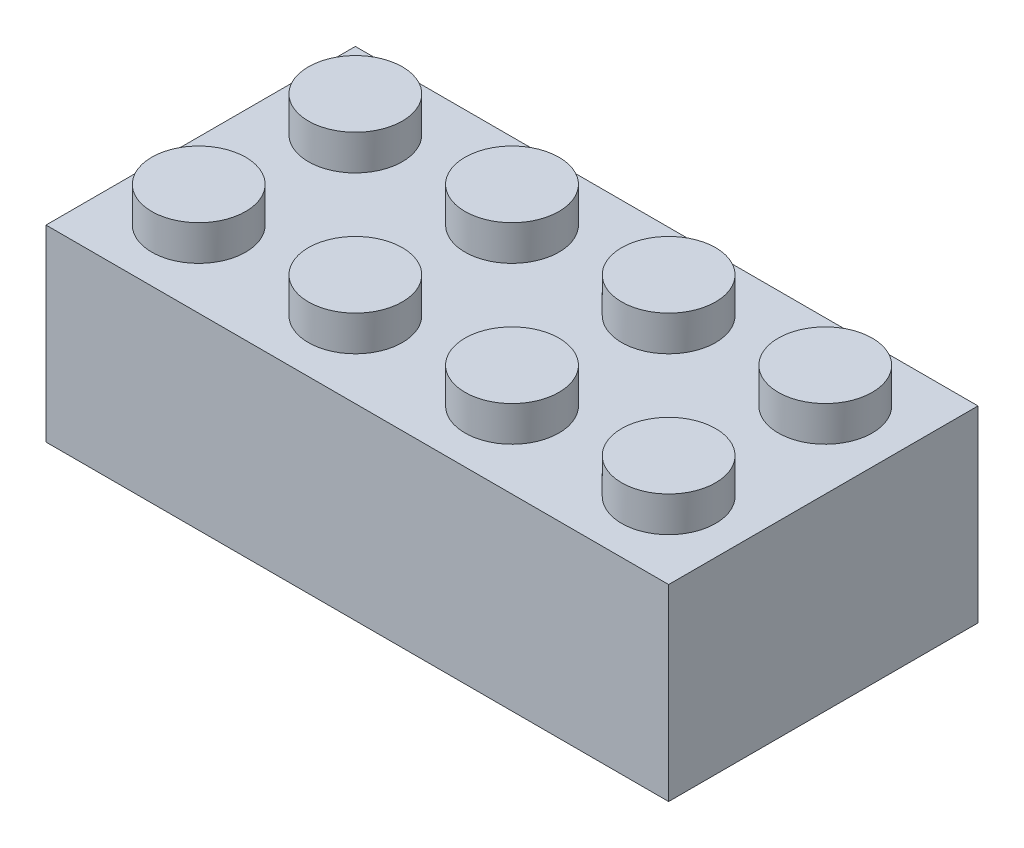
SolidWorks part; units mm, degrees
ref_plane "Front Plane" through (0, 0, 0) normal (0, 0, 1) x (1, 0, 0)
ref_plane "Top Plane" through (0, 0, 0) normal (0, 1, 0) x (1, 0, 0)
ref_plane "Right Plane" through (0, 0, 0) normal (1, 0, 0) x (0, 0, -1)
sketch "Sketch1" plane through (0, 0, 0) normal (0, 1, 0) x (1, 0, 0)
  line L1 (0, 0) -> (31.8, 0)
  line L2 (0, 0) -> (0, 15.8)
  line L3 (0, 15.8) -> (31.8, 15.8)
  line L4 (31.8, 0) -> (31.8, 15.8)
  dimension "D1" = 31.8
  dimension "D2" = 15.8
extrude "Boss-Extrude1" add sketch "Sketch1" along normal blind 9.6
shell "Shell1" thickness 1.2 removed face at (15.9, 0, -7.9)
sketch "Sketch2" plane through (0, 9.6, 0) normal (0, 1, 0) x (1, 0, 0)
  line L0 (31.8, 0) -> (31.8, 15.8) construction
  line L1 (31.8, 15.8) -> (0, 15.8) construction
  circle A0 centre (27.9, 11.9) radius 2.4
  circle A1 centre (19.9, 11.9) radius 2.4
  circle A2 centre (11.9, 11.9) radius 2.4
  circle A3 centre (3.9, 11.9) radius 2.4
  circle A4 centre (19.9, 3.9) radius 2.4
  circle A5 centre (11.9, 3.9) radius 2.4
  circle A6 centre (3.9, 3.9) radius 2.4
  circle A7 centre (27.9, 3.9) radius 2.4
  dimension "D1" = 4.8
  dimension "D2" = 3.9
  dimension "D3" = 3.9
  dimension "D4" = 4
  dimension "D5" = 2
extrude "Boss-Extrude2" add sketch "Sketch2" along normal blind 1.8
sketch "Sketch3" plane through (0, 8.4, 0) normal (0, -1, 0) x (-1, 0, 0)
  line L0 (0, 15.8) -> (0, 0) construction
  line L5 (0, 0) -> (-31.8, 0) construction
  circle A0 centre (-3.9, 3.9) radius 1.4
  circle A1 centre (-11.9, 3.9) radius 1.4
  circle A2 centre (-19.9, 3.9) radius 1.4
  circle A3 centre (-27.9, 3.9) radius 1.4
  circle A4 centre (-11.9, 11.9) radius 1.4
  circle A5 centre (-19.9, 11.9) radius 1.4
  circle A6 centre (-27.9, 11.9) radius 1.4
  circle A7 centre (-3.9, 11.9) radius 1.4
  dimension "D1" = 2.8
  dimension "D2" = 3.9
  dimension "D3" = 3.9
  dimension "D4" = 4
  dimension "D5" = 2
extrude "Cut-Extrude1" cut sketch "Sketch3" against normal blind 1.7
ref_plane "Plane1" through (30.6, 8.4, -1.2) normal (0, 0, -1) x (-1, 0, 0)
sketch "Sketch5" plane through (0, 8.4, 0) normal (0, -1, 0) x (1, 0, 0)
  line L0 (1.2, -8.1839) -> (30.6, -8.1839) construction
  line L1 (1.2, -14.6) -> (1.2, -1.2) construction
  line L2 (30.6, -1.2) -> (30.6, -14.6) construction
  line L3 (30.6, -8.1839) -> (15.9, -8.1839)
  line L4 (15.9, -8.1839) -> (15.9, -14.6) construction
  line L5 (30.6, -14.6) -> (1.2, -14.6) construction
  line L6 (1.2, -1.2) -> (30.6, -1.2) construction
  line L7 (16.3, -14.6) -> (15.5, -14.6)
  line L8 (16.3, -14.6) -> (16.3, -1.2)
  line L9 (16.3, -1.2) -> (15.5, -1.2)
  line L10 (15.5, -14.6) -> (15.5, -1.2)
  line M13 (1.2, -14.6) -> (30.6, -14.6)
  line M15 (30.6, -1.2) -> (1.2, -1.2)
  dimension "D1" = 0.8
  dimension "D2" = 0.4
extrude "Boss-Extrude3" add sketch "Sketch5" along normal blind 6.3 contours L10 L8 M13 M15 region at (15.9, 8.4, -7.9)
